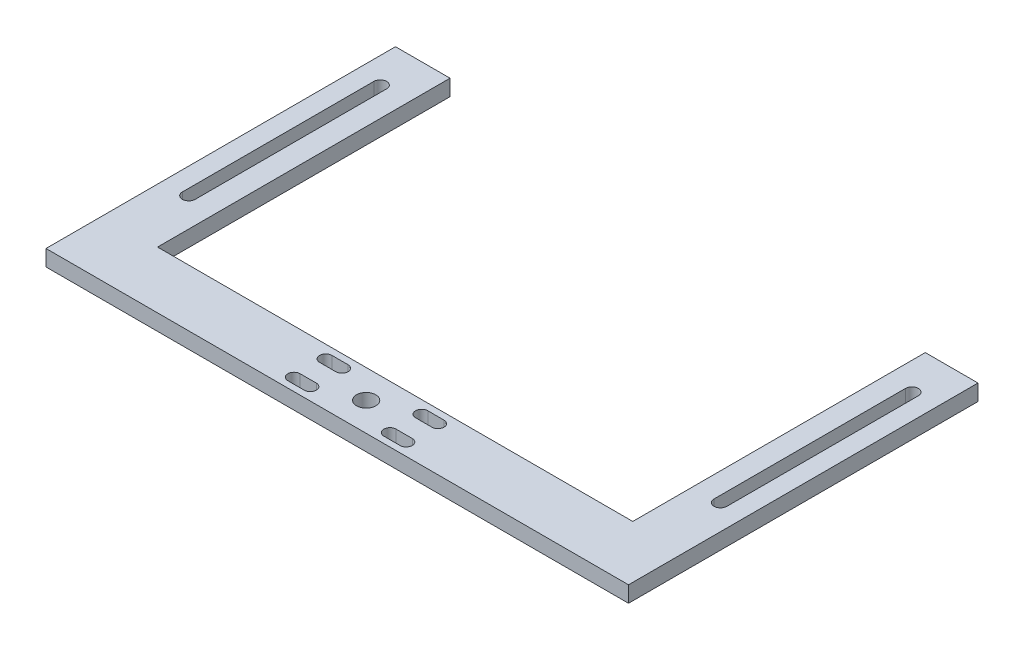
SolidWorks part; units mm, degrees
ref_plane "前视基准面" through (0, 0, 0) normal (0, 0, 1) x (1, 0, 0)
ref_plane "上视基准面" through (0, 0, 0) normal (0, 1, 0) x (1, 0, 0)
ref_plane "右视基准面" through (0, 0, 0) normal (1, 0, 0) x (0, 0, -1)
sketch "草图5" plane through (0, 0, 0) normal (0, 1, 0) x (1, 0, 0)
  line L0 (-10.9135, -27.5952) -> (70.638, -27.5952) construction
  line L1 (-10.9135, -27.5952) -> (-92.5502, -27.5952) construction
  line L2 (-95.0502, 59.6694) -> (-95.0502, 0) construction
  line L8 (-93.0502, 59.6694) -> (-93.0502, 0)
  line L9 (-95.0502, -27.5952) -> (-95.0502, 72.4048) construction
  line L10 (39.0557, -36.5015) -> (-36.6171, -36.5015) construction
  line L11 (-29.6663, -22.7104) -> (-24.5967, -22.7104) construction
  line L12 (70.638, -27.5952) -> (70.638, 72.4048)
  line L13 (39.0557, -36.5015) -> (-36.6171, -36.5015)
  line L16 (27.0317, -27.5952) -> (-30.8458, -27.5952) construction
  line L22 (-103.0436, -27.5952) -> (-103.0436, 72.4048) construction
  line L23 (-103.0436, 72.4048) -> (-86.0436, 72.4048) construction
  line L28 (-86.0436, 72.4048) -> (-86.0436, -27.5952) construction
  line L29 (78.4778, -27.5952) -> (78.4778, 72.4048) construction
  line L33 (78.4778, 72.4048) -> (62.0475, 72.4048) construction
  line L38 (62.0475, 72.4048) -> (62.0475, -27.5952) construction
  line L39 (78.4778, -18.7421) -> (-100.5436, -18.7421)
  line L46 (-24.5967, -18.7421) -> (26.8113, -18.7421)
  line L47 (-103.0436, -18.7421) -> (-103.0436, -36.5015)
  line L48 (-100.5436, -36.5015) -> (78.4778, -36.5015)
  line L49 (78.4778, -36.5015) -> (78.4778, -18.7421)
  line L50 (-97.0502, 59.6694) -> (-97.0502, 0)
  line L51 (70.638, 59.6694) -> (70.638, 0) construction
  line L52 (72.638, 59.6694) -> (72.638, 0)
  line L53 (68.638, 59.6694) -> (68.638, 0)
  line L54 (-103.0436, 29.8347) -> (78.4778, 29.8347)
  line L55 (-103.0436, 72.4048) -> (-86.0436, 72.4048)
  line L56 (-103.0436, 72.4048) -> (-103.0436, -36.5015)
  line L57 (-103.0436, -36.5015) -> (-86.0436, -36.5015)
  line L58 (-86.0436, 72.4048) -> (-86.0436, -36.5015)
  line L59 (62.0475, 72.4048) -> (78.4778, 72.4048)
  line L60 (62.0475, 72.4048) -> (62.0475, -36.5015)
  line L61 (62.0475, -36.5015) -> (78.4778, -36.5015)
  line L62 (78.4778, 72.4048) -> (78.4778, -36.5015)
  line L63 (-12.2829, 29.8347) -> (-12.2829, -81.1273) construction
  line L64 (-29.6663, -20.8099) -> (-24.5967, -20.8099)
  line L65 (-29.6663, -24.6109) -> (-24.5967, -24.6109)
  line L66 (-29.6663, -32.6094) -> (-24.5967, -32.6094) construction
  line L67 (-29.6663, -30.7094) -> (-24.5967, -30.7094)
  line L68 (-29.6663, -34.5094) -> (-24.5967, -34.5094)
  line L69 (0.2332, -22.7099) -> (5.3028, -22.7099) construction
  line L70 (0.2332, -20.8099) -> (5.3028, -20.8099)
  line L71 (0.2332, -24.6099) -> (5.3028, -24.6099)
  line L72 (0.2332, -32.6094) -> (5.3028, -32.6094) construction
  line L73 (0.2332, -30.7094) -> (5.3028, -30.7094)
  line L74 (0.2332, -34.5094) -> (5.3028, -34.5094)
  circle A0 centre (-12.1836, -27.5952) radius 3
  arc A9 (-93.0502, 59.6694) -> (-97.0502, 59.6694) centre (-95.0502, 59.6694) ccw
  arc A10 (-97.0502, 0) -> (-93.0502, 0) centre (-95.0502, 0) ccw
  arc A11 (72.638, 59.6694) -> (68.638, 59.6694) centre (70.638, 59.6694) ccw
  arc A12 (68.638, 0) -> (72.638, 0) centre (70.638, 0) ccw
  arc A13 (-29.6663, -20.8099) -> (-29.6663, -24.6109) centre (-29.6663, -22.7104) ccw
  arc A14 (-24.5967, -24.6109) -> (-24.5967, -20.8099) centre (-24.5967, -22.7104) ccw
  arc A15 (-29.6663, -30.7094) -> (-29.6663, -34.5094) centre (-29.6663, -32.6094) ccw
  arc A16 (-24.5967, -34.5094) -> (-24.5967, -30.7094) centre (-24.5967, -32.6094) ccw
  arc A17 (0.2332, -20.8099) -> (0.2332, -24.6099) centre (0.2332, -22.7099) ccw
  arc A18 (5.3028, -24.6099) -> (5.3028, -20.8099) centre (5.3028, -22.7099) ccw
  arc A19 (0.2332, -30.7094) -> (0.2332, -34.5094) centre (0.2332, -32.6094) ccw
  arc A20 (5.3028, -34.5094) -> (5.3028, -30.7094) centre (5.3028, -32.6094) ccw
  point P2 (-0.161, 4.1382)
  point P8 (-0.161, 4.1382)
  point P19 (-27.1315, -22.7104)
  point P26 (-1, -27.5952)
  point P27 (-27.1315, -32.6094)
  point P44 (-0.161, 4.1382)
  point P46 (-95.0502, 29.8347)
  point P53 (70.638, 29.8347)
  point P56 (-0.161, 4.1382)
  point P69 (2.768, -22.7099)
  point P75 (2.768, -32.6094)
extrude "凸台-拉伸4" add sketch "草图5" along normal blind 5 contours L46 L13 A0 A9 | L56 L55 L58 L57 | L60 L59 L62 L61 region at (-55.3201, 0, 20.2337)
extrude "切除-拉伸2" cut sketch "草图5<14>" against normal mid plane 17 contours L50 A10 L8 A9
sketch "草图5<14>" plane through (0, 0, 0) normal (0, 1, 0) x (1, 0, 0) same geometry as "草图5"
extrude "切除-拉伸4" cut sketch "草图5<16>" against normal mid plane 17 contours L52 A12 L53 A11
sketch "草图5<16>" plane through (0, 0, 0) normal (0, 1, 0) x (1, 0, 0) same geometry as "草图5"
